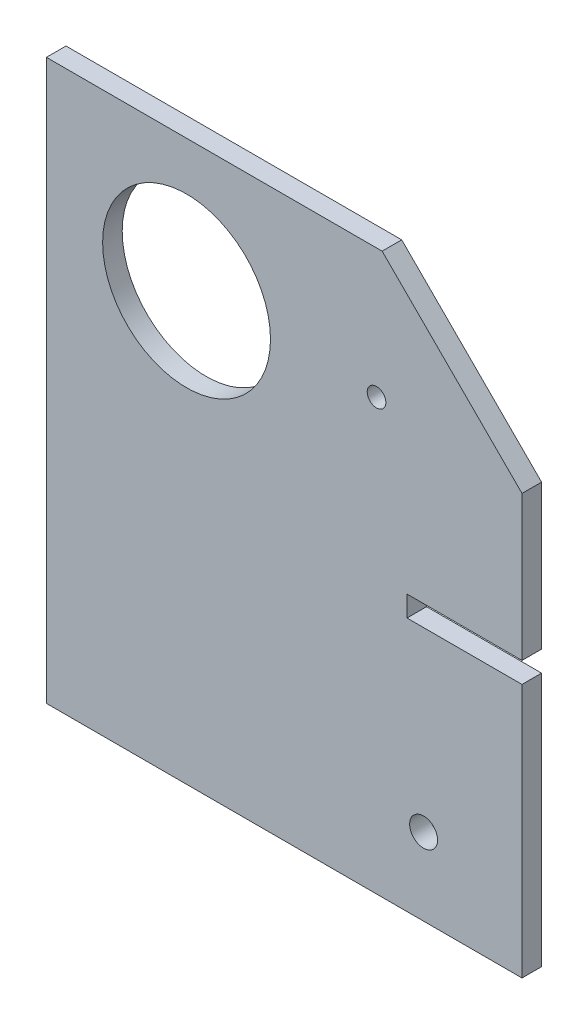
SolidWorks part; units mm, degrees
ref_plane "Front Plane" through (0, 0, 0) normal (0, 0, 1) x (1, 0, 0)
ref_plane "Top Plane" through (0, 0, 0) normal (0, 1, 0) x (1, 0, 0)
ref_plane "Right Plane" through (0, 0, 0) normal (1, 0, 0) x (0, 0, -1)
sketch "Sketch1" plane through (0, 0, 0) normal (0, 0, 1) x (1, 0, 0)
  line L1 (-13.3232, 13.2625) -> (156.6768, 13.2625)
  line L2 (-13.3232, 13.2625) -> (-13.3232, -186.7375)
  line L3 (-13.3232, -186.7375) -> (156.6768, -186.7375)
  line L4 (156.6768, 13.2625) -> (156.6768, -186.7375)
  dimension "D1" = 170
  dimension "D2" = 200
extrude "Boss-Extrude1" add sketch "Sketch1" along normal blind 7
chamfer "Chamfer1" distance 50 angle 45 1 edges at (156.6768, 13.2625, 3.5)
sketch "Sketch2" plane through (0, 0, 7) normal (0, 0, 1) x (1, 0, 0)
  line L0 (156.6768, -186.7375) -> (156.6768, -36.7375) construction
  line L1 (156.6768, -88.4342) -> (115.5612, -88.4342)
  line L2 (156.6768, -88.4342) -> (156.6768, -95.8583)
  line L3 (156.6768, -95.8583) -> (115.5612, -95.8583)
  line L4 (115.5612, -88.4342) -> (115.5612, -95.8583)
  circle A0 centre (104.6726, -32.9544) radius 3.3253
  circle A1 centre (121.5004, -159.1632) radius 4.9921
  point P10 (104.6726, -32.9544)
  point P11 (121.5004, -159.1632)
extrude "Cut-Extrude1" cut sketch "Sketch2" against normal blind 10
sketch "Sketch3" plane through (0, 0, 7) normal (0, 0, 1) x (1, 0, 0)
  circle A0 centre (36.7707, -33.9912) radius 30
  point P2 (36.7707, -33.9912)
extrude "Cut-Extrude2" cut sketch "Sketch3" against normal blind 10
